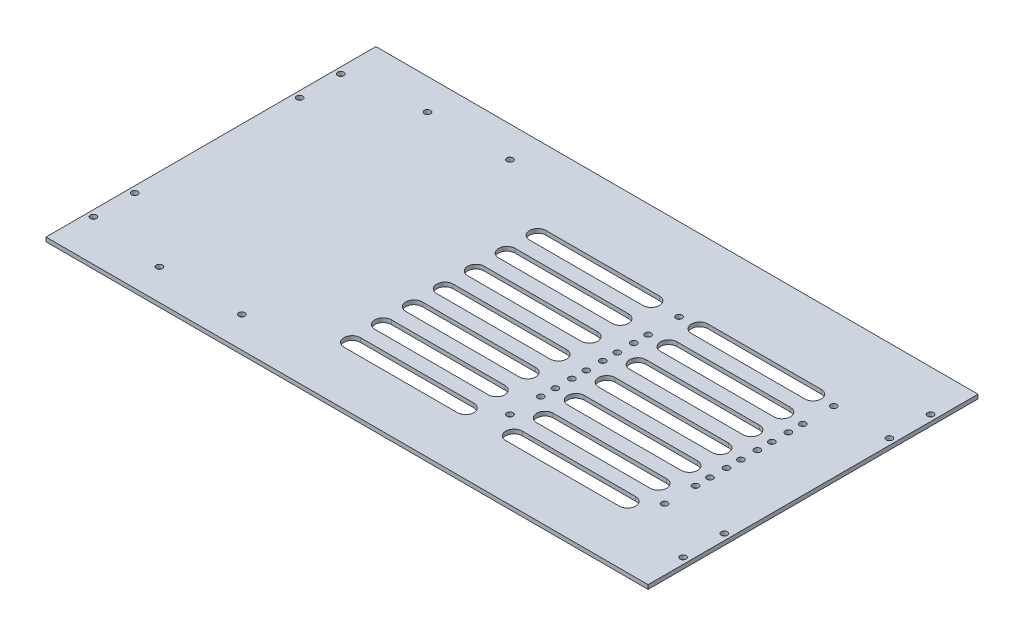
SolidWorks part; units mm, degrees
material "Thornel Mat VMA"
ref_plane "前视基准面" through (0, 0, 0) normal (0, 0, 1) x (1, 0, 0)
ref_plane "上视基准面" through (0, 0, 0) normal (0, 1, 0) x (1, 0, 0)
ref_plane "右视基准面" through (0, 0, 0) normal (1, 0, 0) x (0, 0, -1)
sketch "草图1" plane through (0, 0, 0) normal (0, 1, 0) x (1, 0, 0)
  line L0 (3, 40) -> (3, 20) construction
  line L1 (0, 0) -> (292, 0)
  line L2 (0, 0) -> (0, 160)
  line L3 (0, 160) -> (292, 160)
  line L4 (292, 0) -> (292, 160)
  line L5 (3, 140) -> (3, 120) construction
  line L6 (146, 160) -> (146, 0) construction
  line L7 (289, 40) -> (289, 20) construction
  line L8 (289, 140) -> (289, 120) construction
  line L9 (0, 80) -> (30, 80) construction
  line L14 (197, 120) -> (252, 120) construction
  line L15 (187, 120) -> (262, 120) construction
  line L16 (187, 120) -> (187, 98) construction
  line L17 (187, 98) -> (262, 98) construction
  line L18 (262, 120) -> (262, 98) construction
  line L19 (40, 145) -> (80, 145) construction
  line L20 (40, 145) -> (40, 15) construction
  line L21 (40, 15) -> (80, 15) construction
  line L22 (80, 145) -> (80, 15) construction
  line L27 (197, 124) -> (252, 124)
  line L28 (197, 116) -> (252, 116)
  line L29 (197, 101) -> (252, 101)
  line L30 (197, 109) -> (252, 109)
  line L31 (197, 105) -> (252, 105) construction
  line L32 (197, 86) -> (252, 86)
  line L33 (197, 94) -> (252, 94)
  line L34 (197, 90) -> (252, 90) construction
  line L35 (197, 71) -> (252, 71)
  line L36 (197, 79) -> (252, 79)
  line L37 (197, 75) -> (252, 75) construction
  line L38 (197, 56) -> (252, 56)
  line L39 (197, 64) -> (252, 64)
  line L40 (197, 60) -> (252, 60) construction
  line L41 (197, 45) -> (252, 45) construction
  line L42 (197, 49) -> (252, 49)
  line L43 (197, 41) -> (252, 41)
  line L44 (197, 30) -> (252, 30) construction
  line L45 (197, 34) -> (252, 34)
  line L46 (197, 26) -> (252, 26)
  line L47 (118.5, 116) -> (173.5, 116)
  line L48 (118.5, 124) -> (173.5, 124)
  line L49 (118.5, 109) -> (173.5, 109)
  line L50 (118.5, 101) -> (173.5, 101)
  line L51 (118.5, 94) -> (173.5, 94)
  line L52 (118.5, 86) -> (173.5, 86)
  line L53 (118.5, 79) -> (173.5, 79)
  line L54 (118.5, 71) -> (173.5, 71)
  line L55 (118.5, 64) -> (173.5, 64)
  line L56 (118.5, 56) -> (173.5, 56)
  line L57 (118.5, 49) -> (173.5, 49)
  line L58 (118.5, 41) -> (173.5, 41)
  line L59 (118.5, 34) -> (173.5, 34)
  line L60 (118.5, 26) -> (173.5, 26)
  line L61 (118.5, 120) -> (173.5, 120) construction
  line L62 (118.5, 105) -> (173.5, 105) construction
  line L63 (118.5, 90) -> (173.5, 90) construction
  line L64 (118.5, 75) -> (173.5, 75) construction
  line L65 (118.5, 60) -> (173.5, 60) construction
  line L66 (118.5, 45) -> (173.5, 45) construction
  line L67 (118.5, 30) -> (173.5, 30) construction
  circle A0 centre (3, 140) radius 1.5
  circle A1 centre (3, 120) radius 1.5
  circle A2 centre (3, 40) radius 1.5
  circle A3 centre (3, 20) radius 1.5
  circle A4 centre (289, 20) radius 1.5
  circle A5 centre (289, 40) radius 1.5
  circle A6 centre (289, 120) radius 1.5
  circle A7 centre (289, 140) radius 1.5
  circle A8 centre (187, 120) radius 1.5
  circle A9 centre (262, 120) radius 1.5
  circle A10 centre (262, 98) radius 1.5
  circle A11 centre (187, 98) radius 1.5
  circle A12 centre (187, 105) radius 1.5
  circle A13 centre (262, 105) radius 1.5
  circle A14 centre (187, 83) radius 1.5
  circle A15 centre (262, 83) radius 1.5
  circle A16 centre (187, 90) radius 1.5
  circle A17 centre (262, 90) radius 1.5
  circle A18 centre (187, 68) radius 1.5
  circle A19 centre (262, 68) radius 1.5
  circle A20 centre (187, 75) radius 1.5
  circle A21 centre (262, 75) radius 1.5
  circle A22 centre (187, 53) radius 1.5
  circle A23 centre (262, 53) radius 1.5
  circle A24 centre (187, 60) radius 1.5
  circle A25 centre (262, 60) radius 1.5
  circle A26 centre (187, 38) radius 1.5
  circle A27 centre (262, 38) radius 1.5
  circle A28 centre (40, 145) radius 1.5
  circle A29 centre (80, 145) radius 1.5
  circle A30 centre (40, 15) radius 1.5
  circle A31 centre (80, 15) radius 1.5
  arc A32 (197, 124) -> (197, 116) centre (197, 120) ccw
  arc A33 (252, 116) -> (252, 124) centre (252, 120) ccw
  arc A34 (197, 109) -> (197, 101) centre (197, 105) ccw
  arc A35 (252, 101) -> (252, 109) centre (252, 105) ccw
  arc A36 (197, 94) -> (197, 86) centre (197, 90) ccw
  arc A37 (252, 86) -> (252, 94) centre (252, 90) ccw
  arc A38 (197, 79) -> (197, 71) centre (197, 75) ccw
  arc A39 (252, 71) -> (252, 79) centre (252, 75) ccw
  arc A40 (197, 64) -> (197, 56) centre (197, 60) ccw
  arc A41 (252, 56) -> (252, 64) centre (252, 60) ccw
  arc A42 (197, 49) -> (197, 41) centre (197, 45) ccw
  arc A43 (252, 41) -> (252, 49) centre (252, 45) ccw
  arc A44 (197, 34) -> (197, 26) centre (197, 30) ccw
  arc A45 (252, 26) -> (252, 34) centre (252, 30) ccw
  arc A46 (118.5, 124) -> (118.5, 116) centre (118.5, 120) ccw
  arc A47 (173.5, 116) -> (173.5, 124) centre (173.5, 120) ccw
  arc A48 (173.5, 101) -> (173.5, 109) centre (173.5, 105) ccw
  arc A49 (118.5, 109) -> (118.5, 101) centre (118.5, 105) ccw
  arc A50 (173.5, 86) -> (173.5, 94) centre (173.5, 90) ccw
  arc A51 (118.5, 94) -> (118.5, 86) centre (118.5, 90) ccw
  arc A52 (173.5, 71) -> (173.5, 79) centre (173.5, 75) ccw
  arc A53 (118.5, 79) -> (118.5, 71) centre (118.5, 75) ccw
  arc A54 (173.5, 56) -> (173.5, 64) centre (173.5, 60) ccw
  arc A55 (118.5, 64) -> (118.5, 56) centre (118.5, 60) ccw
  arc A56 (173.5, 41) -> (173.5, 49) centre (173.5, 45) ccw
  arc A57 (118.5, 49) -> (118.5, 41) centre (118.5, 45) ccw
  arc A58 (173.5, 26) -> (173.5, 34) centre (173.5, 30) ccw
  arc A59 (118.5, 34) -> (118.5, 26) centre (118.5, 30) ccw
  point P79 (224.5, 120)
  point P89 (224.5, 105)
  point P96 (224.5, 90)
  point P103 (224.5, 75)
  point P110 (224.5, 60)
  point P117 (224.5, 45)
  point P123 (224.5, 30)
  point P129 (146, 120)
  point P137 (146, 105)
  point P144 (146, 90)
  point P151 (146, 75)
  point P158 (146, 60)
  point P165 (146, 45)
  point P171 (146, 30)
  dimension "D3" = 20
  dimension "D5" = 3
  dimension "D7" = 20
  dimension "D14" = 3
  dimension "D23" = 3
  dimension "D26" = 4
  dimension "D1" = 292
  dimension "D2" = 160
  dimension "D4" = 3
  dimension "D6" = 20
  dimension "D8" = 20
  dimension "D12" = 22
  dimension "D13" = 75
  dimension "D15" = 40
  dimension "D16" = 30
  dimension "D18" = 15
  dimension "D19" = 15
  dimension "D20" = 15
  dimension "D24" = 10
  dimension "D25" = 10
  dimension "D28" = 15
  dimension "D17" = 5
  dimension "D27" = 3
  dimension "D29" = 2
extrude "凸台-拉伸1" add sketch "草图1" along normal blind 2
